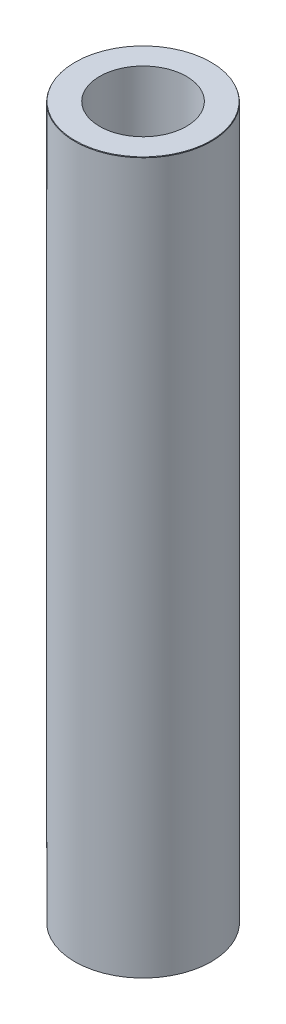
SolidWorks part; units mm, degrees
ref_plane "Front Plane" through (0, 0, 0) normal (0, 0, 1) x (1, 0, 0)
ref_plane "Top Plane" through (0, 0, 0) normal (0, 1, 0) x (1, 0, 0)
ref_plane "Right Plane" through (0, 0, 0) normal (1, 0, 0) x (0, 0, -1)
sketch "Sketch1" plane through (0, 0, 0) normal (0, 1, 0) x (1, 0, 0)
  circle A0 centre (0, 0) radius 47.5
  dimension "SHAFT_OD" = 95
extrude "Boss-Extrude1" add sketch "Sketch1" along normal blind 495.3664
sketch "Sketch2" plane through (0, 0, 0) normal (0, 1, 0) x (1, 0, 0)
  circle A0 centre (0, 0) radius 30.2171
  dimension "BORE_D" = 60.4343
extrude "Cut-Extrude1" cut sketch "Sketch2" along normal through all
chamfer "Chamfer1" distance 0.4609 angle 21.163 2 edges at (0, 495.3664, 47.5) (0, 0, 47.5) first distance on face at (0, 495.3664, 47.5) first distance on face at (0, 0, 30.2171)
